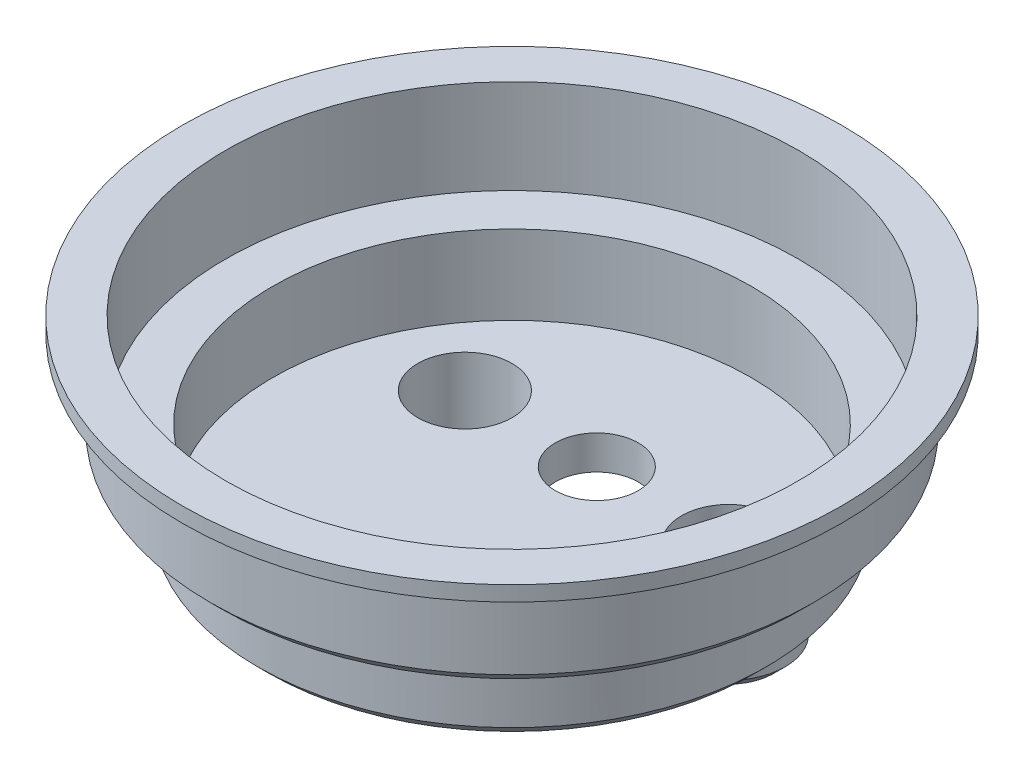
SolidWorks part; units mm, degrees
material "PBT General Purpose"
ref_plane "Front Plane" through (0, 0, 0) normal (0, 0, 1) x (1, 0, 0)
ref_plane "Top Plane" through (0, 0, 0) normal (0, 1, 0) x (1, 0, 0)
ref_plane "Right Plane" through (0, 0, 0) normal (1, 0, 0) x (0, 0, -1)
sketch "Sketch1" plane through (0, 0, 0) normal (0, 1, 0) x (1, 0, 0)
  circle A0 centre (0, 0) radius 67.5
  dimension "D1" = 135
extrude "Boss-Extrude1" add sketch "Sketch1" along normal blind 21
sketch "Sketch3" plane through (0, 21, 0) normal (0, 1, 0) x (1, 0, 0)
  circle A0 centre (0, 0) radius 80
  dimension "D1" = 160
extrude "Boss-Extrude2" add sketch "Sketch3" along normal blind 25
sketch "Sketch4" plane through (0, 46, 0) normal (0, 1, 0) x (1, 0, 0)
  circle A0 centre (0, 0) radius 87.5
  dimension "D1" = 175
extrude "Boss-Extrude3" add sketch "Sketch4" along normal blind 4
shell "Shell1" thickness 4 removed face at (0, 50, 87.5)
sketch "Sketch2" plane through (0, 4, 0) normal (0, 1, 0) x (1, 0, 0)
  line L0 (0, 0) -> (0, 22.5) construction
  line L1 (-35, 22.5) -> (35, 22.5) construction
  circle A0 centre (0, 22.5) radius 11
  circle A1 centre (-35, 22.5) radius 6.25
  circle A2 centre (35, 22.5) radius 6.25
  dimension "D1" = 22
  dimension "D4" = 12.5
  dimension "D2" = 22.5
  dimension "D3" = 70
extrude "Cut-Extrude1" cut sketch "Sketch2" against normal blind 10
sketch "Sketch5" plane through (0, 0, 0) normal (0, -1, 0) x (1, 0, 0)
  circle A0 centre (35, -22.5) radius 15
  circle A1 centre (-35, -22.5) radius 15
  circle A2 centre (-35, -22.5) radius 6.25 construction
  circle A3 centre (35, -22.5) radius 6.25 construction
  circle A4 centre (-35, -22.5) radius 6.25
  circle A5 centre (35, -22.5) radius 6.25
  dimension "D1" = 30
extrude "Boss-Extrude4" add sketch "Sketch5" along normal blind 20
sketch "Sketch6" plane through (0, 4, 0) normal (0, 1, 0) x (1, 0, 0)
  circle A0 centre (-35, 22.5) radius 12.5
  circle A1 centre (35, 22.5) radius 12.5
  dimension "D1" = 25
extrude "Cut-Extrude2" cut sketch "Sketch6" against normal blind 20
chamfer "Chamfer1" distance 3 angle 45 2 edges at (0, 0, 67.5) (0, 21, 80)
chamfer "Chamfer2" distance 3 angle 45 2 edges at (-35, -20, -37.5) (35, -20, -37.5)
sketch "Sketch7" plane through (0, 0, 0) normal (0, -1, 0) x (1, 0, 0)
  circle A0 centre (0, -22.5) radius 15
  circle A1 centre (0, -22.5) radius 11
  circle A2 centre (0, -22.5) radius 11 construction
  dimension "D1" = 30
extrude "Boss-Extrude5" add sketch "Sketch7" along normal blind 5
